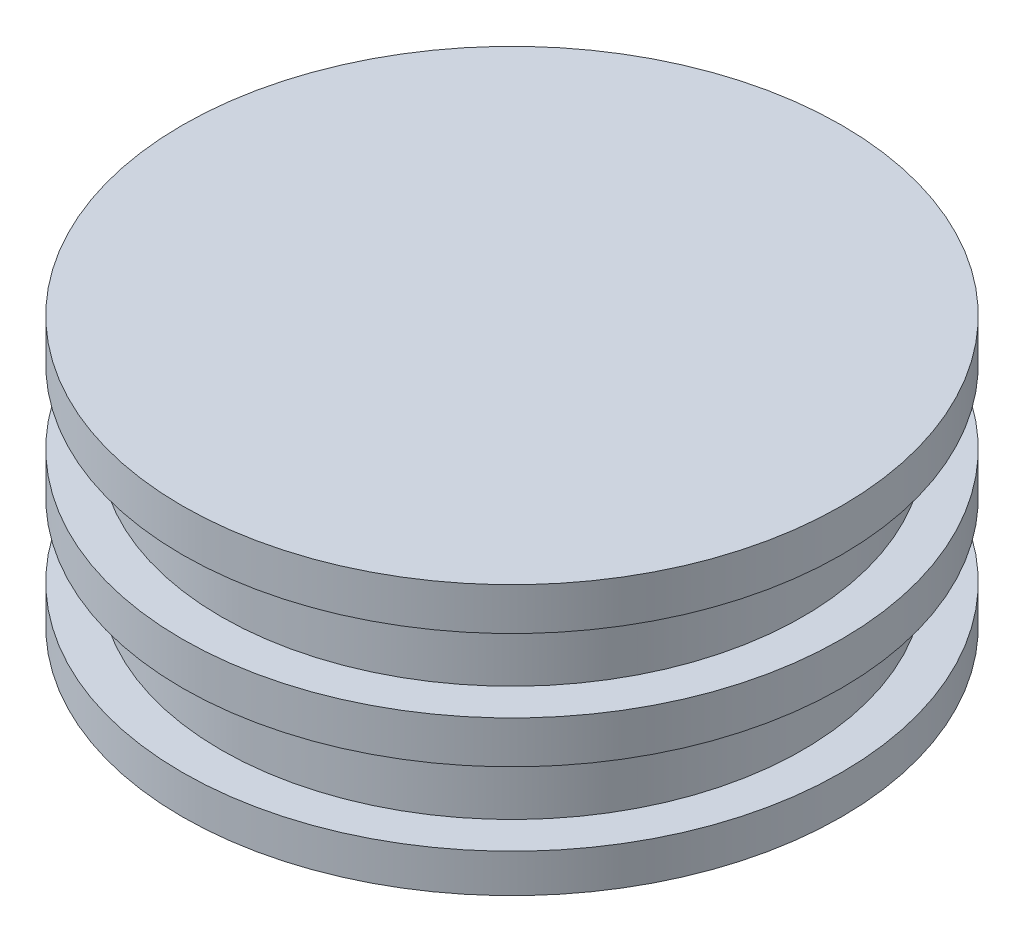
SolidWorks part; units mm, degrees
material "AISI 304"
ref_plane "Front Plane" through (0, 0, 0) normal (0, 0, 1) x (1, 0, 0)
ref_plane "Top Plane" through (0, 0, 0) normal (0, 1, 0) x (1, 0, 0)
ref_plane "Right Plane" through (0, 0, 0) normal (1, 0, 0) x (0, 0, -1)
ref_axis "Axis1" through (0, 21.1841, 0) along (0, -1, 0)
sketch "Sketch1" plane through (0, 0, 0) normal (0, 1, 0) x (1, 0, 0)
  circle A0 centre (0, 0) radius 10.8839
  dimension "D1" = 21.7678
extrude "Boss-Extrude1" add sketch "Sketch1" along normal blind 8.89
sketch "Sketch4" plane through (0, 0, 0) normal (0, 0, 1) x (1, 0, 0)
  line L0 (10.8839, 8.89) -> (-10.8839, 8.89) construction
  line L1 (9.6012, 3.683) -> (12.0142, 3.683)
  line L2 (9.6012, 3.683) -> (9.6012, 1.27)
  line L3 (9.6012, 1.27) -> (12.0142, 1.27)
  line L4 (12.0142, 3.683) -> (12.0142, 1.27)
  line L5 (10.8839, 9.7299) -> (10.8839, 50009.7299) construction
  line L6 (0, 0) -> (0, 50000) construction
  line L7 (0, 0) -> (-50000, 0) construction
  point P11 (10.8839, 8.89)
  dimension "D1" = 1.27
  dimension "D2" = 9.6012
  dimension "D3" = 2.413
revolve "Cut-Revolve1" cut sketch "Sketch4" angle 360 about L6
pattern_linear "LPattern1" count 2 spacing 3.81 along (0, 1, 0) of "Cut-Revolve1"
